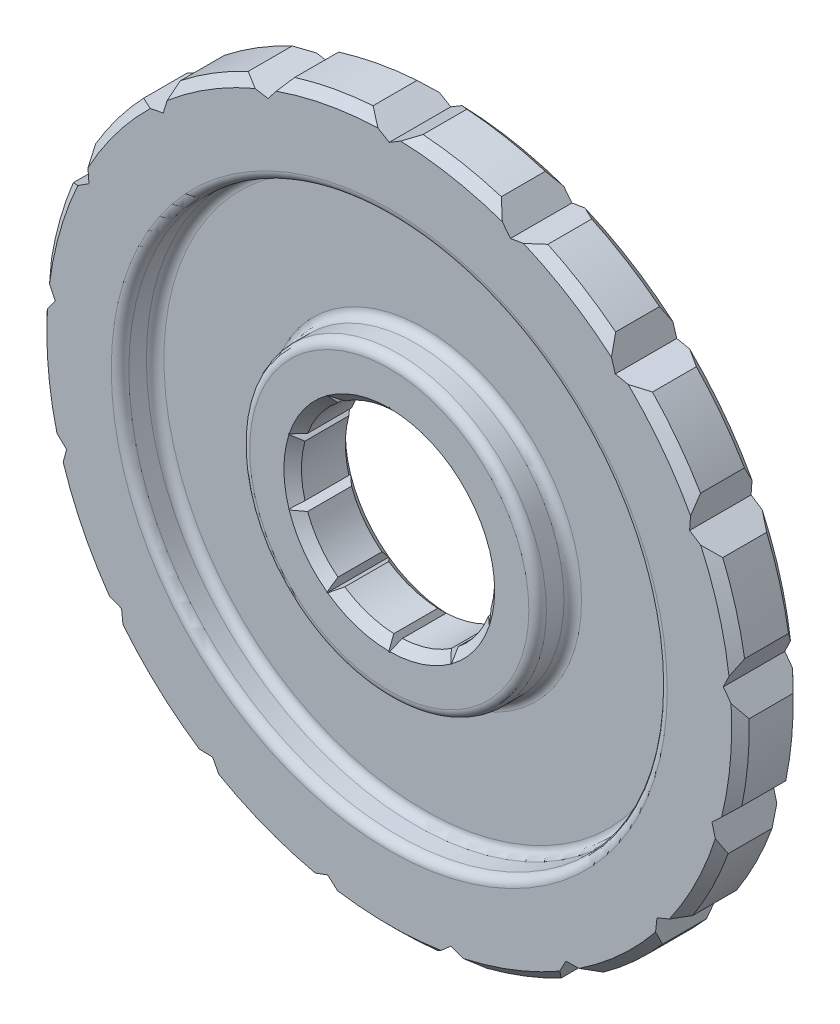
SolidWorks part; units mm, degrees
ref_plane "Front Plane" through (0, 0, 0) normal (0, 0, 1) x (1, 0, 0)
ref_plane "Top Plane" through (0, 0, 0) normal (0, 1, 0) x (1, 0, 0)
ref_plane "Right Plane" through (0, 0, 0) normal (1, 0, 0) x (0, 0, -1)
sketch "Sketch1" plane through (0, 0, 0) normal (0, 0, 1) x (1, 0, 0)
  circle A0 centre (0, 0) radius 11
  circle A1 centre (0, 0) radius 40
  dimension "D1" = 22
  dimension "D2" = 80
extrude "Boss-Extrude1" add sketch "Sketch1" along normal blind 7
chamfer "Chamfer1" distance 1 angle 45 4 edges at (40, 0, 0) (40, 0, 7) (11, 0, 0) (11, 0, 7)
sketch "Sketch2" plane through (0, 0, 7) normal (0, 0, 1) x (1, 0, 0)
  line L0 (0, 0) -> (0, 34.5062) construction
  line L1 (0, 12.1033) -> (-0.887, 10.0504)
  line L2 (-0.887, 10.0504) -> (0.887, 10.0504)
  line L3 (0.887, 10.0504) -> (0, 12.1033)
  line L4 (6.6251, 7.6096) -> (7.1141, 9.7917)
  line L5 (7.1141, 9.7917) -> (5.1899, 8.6523)
  line L6 (5.1899, 8.6523) -> (6.6251, 7.6096)
  line L7 (9.8326, 2.2622) -> (11.5109, 3.7401)
  line L8 (11.5109, 3.7401) -> (9.2844, 3.9493)
  line L9 (9.2844, 3.9493) -> (9.8326, 2.2622)
  line L10 (9.2844, -3.9493) -> (11.5109, -3.7401)
  line L11 (11.5109, -3.7401) -> (9.8326, -2.2622)
  line L12 (9.8326, -2.2622) -> (9.2844, -3.9493)
  line L13 (5.1899, -8.6523) -> (7.1141, -9.7917)
  line L14 (7.1141, -9.7917) -> (6.6251, -7.6096)
  line L15 (6.6251, -7.6096) -> (5.1899, -8.6523)
  line L16 (-0.887, -10.0504) -> (0, -12.1033)
  line L17 (0, -12.1033) -> (0.887, -10.0504)
  line L18 (0.887, -10.0504) -> (-0.887, -10.0504)
  line L19 (-6.6251, -7.6096) -> (-7.1141, -9.7917)
  line L20 (-7.1141, -9.7917) -> (-5.1899, -8.6523)
  line L21 (-5.1899, -8.6523) -> (-6.6251, -7.6096)
  line L22 (-9.8326, -2.2622) -> (-11.5109, -3.7401)
  line L23 (-11.5109, -3.7401) -> (-9.2844, -3.9493)
  line L24 (-9.2844, -3.9493) -> (-9.8326, -2.2622)
  line L25 (-9.2844, 3.9493) -> (-11.5109, 3.7401)
  line L26 (-11.5109, 3.7401) -> (-9.8326, 2.2622)
  line L27 (-9.8326, 2.2622) -> (-9.2844, 3.9493)
  line L28 (-5.1899, 8.6523) -> (-7.1141, 9.7917)
  line L29 (-7.1141, 9.7917) -> (-6.6251, 7.6096)
  line L30 (-6.6251, 7.6096) -> (-5.1899, 8.6523)
  line L31 (-4.9611, 41.1614) -> (0, 38.2086)
  line L32 (0, 38.2086) -> (4.9611, 41.1614)
  line L33 (4.9611, 41.1614) -> (-4.9611, 41.1614)
  line L34 (19.4954, 36.5897) -> (10.2431, 40.1741)
  line L35 (10.2431, 40.1741) -> (13.8025, 35.6284)
  line L36 (13.8025, 35.6284) -> (19.4954, 36.5897)
  line L37 (31.3966, 27.0764) -> (24.064, 33.761)
  line L38 (24.064, 33.761) -> (25.7409, 28.2365)
  line L39 (25.7409, 28.2365) -> (31.3966, 27.0764)
  line L40 (39.0576, 13.9062) -> (34.6348, 22.7883)
  line L41 (34.6348, 22.7883) -> (34.2029, 17.031)
  line L42 (34.2029, 17.031) -> (39.0576, 13.9062)
  line L43 (41.4436, -1.1421) -> (40.5281, 8.7379)
  line L44 (40.5281, 8.7379) -> (38.0456, 3.5254)
  line L45 (38.0456, 3.5254) -> (41.4436, -1.1421)
  line L46 (38.2324, -16.0361) -> (40.9478, -6.4926)
  line L47 (40.9478, -6.4926) -> (36.75, -10.4563)
  line L48 (36.75, -10.4563) -> (38.2324, -16.0361)
  line L49 (29.8578, -28.7644) -> (35.8373, -20.8462)
  line L50 (35.8373, -20.8462) -> (30.4911, -23.0258)
  line L51 (30.4911, -23.0258) -> (29.8578, -28.7644)
  line L52 (17.4507, -37.6079) -> (25.8868, -32.3845)
  line L53 (25.8868, -32.3845) -> (20.1142, -32.4856)
  line L54 (20.1142, -32.4856) -> (17.4507, -37.6079)
  line L55 (2.6867, -41.3722) -> (12.4401, -39.549)
  line L56 (12.4401, -39.549) -> (7.0208, -37.558)
  line L57 (7.0208, -37.558) -> (2.6867, -41.3722)
  line L58 (-12.4401, -39.549) -> (-2.6867, -41.3722)
  line L59 (-2.6867, -41.3722) -> (-7.0208, -37.558)
  line L60 (-7.0208, -37.558) -> (-12.4401, -39.549)
  line L61 (-25.8868, -32.3845) -> (-17.4507, -37.6079)
  line L62 (-17.4507, -37.6079) -> (-20.1142, -32.4856)
  line L63 (-20.1142, -32.4856) -> (-25.8868, -32.3845)
  line L64 (-35.8373, -20.8462) -> (-29.8578, -28.7644)
  line L65 (-29.8578, -28.7644) -> (-30.4911, -23.0258)
  line L66 (-30.4911, -23.0258) -> (-35.8373, -20.8462)
  line L67 (-40.9478, -6.4926) -> (-38.2324, -16.0361)
  line L68 (-38.2324, -16.0361) -> (-36.75, -10.4563)
  line L69 (-36.75, -10.4563) -> (-40.9478, -6.4926)
  line L70 (-40.5281, 8.7379) -> (-41.4436, -1.1421)
  line L71 (-41.4436, -1.1421) -> (-38.0456, 3.5254)
  line L72 (-38.0456, 3.5254) -> (-40.5281, 8.7379)
  line L73 (-34.6348, 22.7883) -> (-39.0576, 13.9062)
  line L74 (-39.0576, 13.9062) -> (-34.2029, 17.031)
  line L75 (-34.2029, 17.031) -> (-34.6348, 22.7883)
  line L76 (-24.064, 33.761) -> (-31.3966, 27.0764)
  line L77 (-31.3966, 27.0764) -> (-25.7409, 28.2365)
  line L78 (-25.7409, 28.2365) -> (-24.064, 33.761)
  line L79 (-10.2431, 40.1741) -> (-19.4954, 36.5897)
  line L80 (-19.4954, 36.5897) -> (-13.8025, 35.6284)
  line L81 (-13.8025, 35.6284) -> (-10.2431, 40.1741)
  point P5 (0, 38.2086)
  point P36 (0, 0)
  point P38 (4.9611, 41.1614)
  point P88 (0, 0)
  dimension "D1" = 10
  dimension "D2" = 17
extrude "Cut-Extrude1" cut sketch "Sketch2" against normal blind 7
sketch "Sketch3" plane through (0, 0, 7) normal (0, 0, 1) x (1, 0, 0)
  circle A0 centre (0, 0) radius 16.8965
  circle A1 centre (0, 0) radius 30.6625
extrude "Cut-Extrude2" cut sketch "Sketch3" against normal blind 4
fillet "Fillet1" radius 1 4 edges at (30.6625, 0, 3) (16.8965, 0, 3) (30.6625, 0, 7) (16.8965, 0, 7)
